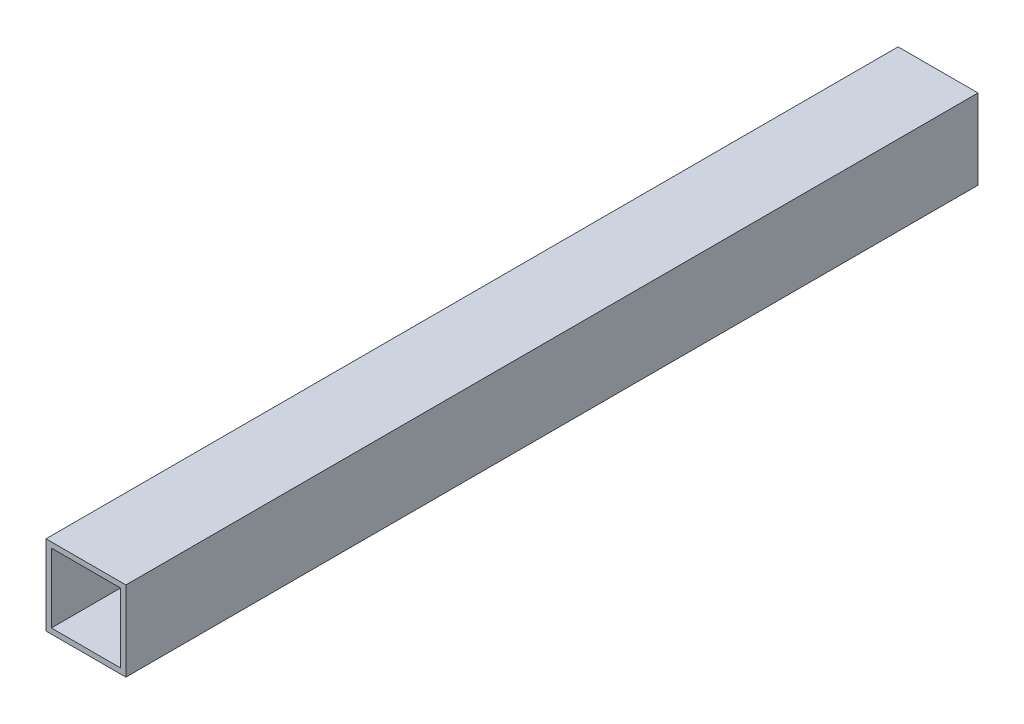
SolidWorks part; units mm, degrees
ref_plane "Front Plane" through (0, 0, 0) normal (0, 0, 1) x (1, 0, 0)
ref_plane "Top Plane" through (0, 0, 0) normal (0, 1, 0) x (1, 0, 0)
ref_plane "Right Plane" through (0, 0, 0) normal (1, 0, 0) x (0, 0, -1)
sketch "Sketch3" plane through (0, 0, 0) normal (0, 0, 1) x (1, 0, 0)
  line L1 (0, 0) -> (15, 0)
  line L2 (0, 0) -> (0, 15)
  line L3 (0, 15) -> (15, 15)
  line L4 (15, 0) -> (15, 15)
  dimension "D1" = 15
extrude "Extrude-Thin1" add sketch "Sketch3" along normal blind 160 thin thin type one direction reverse wall 1
